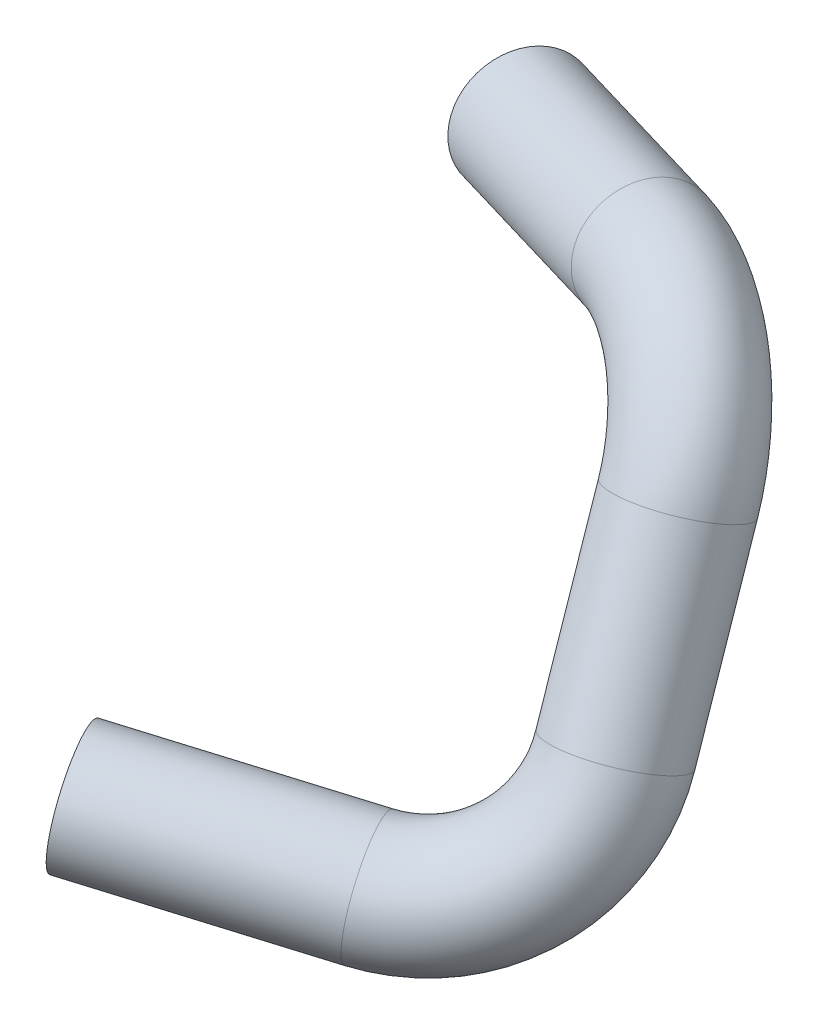
SolidWorks part; units mm, degrees
ref_plane "Piano frontale" through (0, 0, 0) normal (0, 0, 1) x (1, 0, 0)
ref_plane "Piano superiore" through (0, 0, 0) normal (0, 1, 0) x (1, 0, 0)
ref_plane "Piano destro" through (0, 0, 0) normal (1, 0, 0) x (0, 0, -1)
sketch3d "Schizzo3D1"
  line L0 (-10.6694, 12.4725, 10.4932) -> (-9.7161, 3.2339, 14.8686)
  line L1 (-26.8655, -1.3196, 27.3592) -> (-21.5583, -2.1341, 24.6815)
  line L2 (-16.1394, -2.9658, 21.9474) -> (-21.5583, -2.1341, 24.6815)
  line L7 (-17.7519, 18.0203, 5.184) -> (-28.4255, 16.9309, 1.2566)
  arc A0 (-27.5673, 13.2887, -0.0657) -> (-29.2838, 20.5732, 2.5788) centre (-28.4255, 16.9309, 1.2566) ccw construction
  circle A2 centre (-26.8655, -1.3196, 27.3592) radius 3.175 construction
  arc A4 (-16.1394, -2.9658, 21.9474) -> (-9.7161, 3.2339, 14.8686) centre (-16.7826, 4.2186, 18.4873) ccw
  arc A5 (-17.7519, 18.0203, 5.184) -> (-10.6694, 12.4725, 10.4932) centre (-18.1149, 10.6281, 8.2211) ccw
  point P8 (0, 0, 0)
  point P10 (-8.9627, -4.0672, 18.3264)
  point P11 (-24.0571, -1.7506, 25.9423)
  point P12 (-13.1065, 7.5661, 24.7548)
  point P16 (-32.1332, 16.5525, -0.1077)
  point P20 (-11.3097, 18.6778, 7.5545)
  point P21 (-8.5277, 23.4011, 8.0545)
  point P22 (-15.2843, 7.6661, 1.3499)
  dimension "D1" = 8
  dimension "D3" = 22
sweep "Sweep-Sottile1" add path "Schizzo3D1" circular profile diameter 6.35 parameters "D1"=0.85, "D3"=6.35
